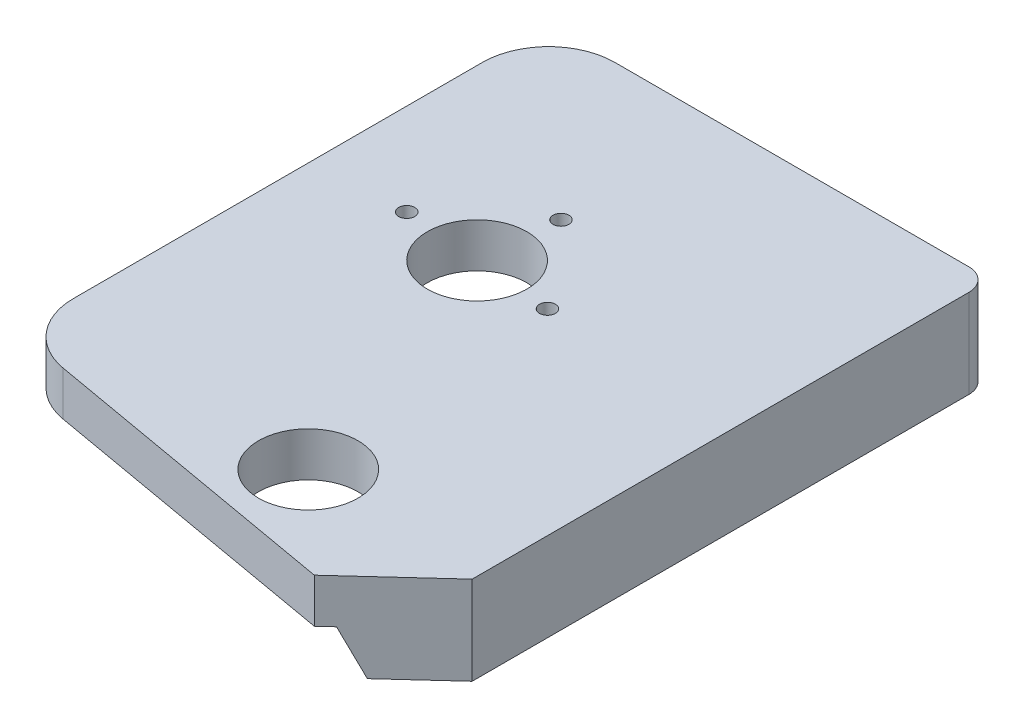
SolidWorks part; units mm, degrees
ref_plane "Front Plane" through (0, 0, 0) normal (0, 0, 1) x (1, 0, 0)
ref_plane "Top Plane" through (0, 0, 0) normal (0, 1, 0) x (1, 0, 0)
ref_plane "Right Plane" through (0, 0, 0) normal (1, 0, 0) x (0, 0, -1)
sketch "Sketch1" plane through (0, 0, 0) normal (0, 1, 0) x (1, 0, 0)
  line L0 (67.846, -67.54) -> (44.1988, -89.2087)
  line L1 (-43.412, -73.7605) -> (44.1988, -89.2087)
  line L2 (-59.154, -54.9999) -> (-59.154, 62.3652)
  line L3 (-40.104, 81.4152) -> (61.496, 81.4152)
  line L4 (67.846, -67.54) -> (67.846, 75.0652)
  line L5 (-59.154, -70.9848) -> (67.846, 81.4152) construction
  line L6 (-59.154, 81.4152) -> (67.846, -93.3783) construction
  line L7 (44.1988, -89.2087) -> (67.846, -93.3783) construction
  line L8 (67.846, -93.3783) -> (67.846, -67.54) construction
  arc A0 (61.496, 81.4152) -> (67.846, 75.0652) centre (61.496, 75.0652) cw
  arc A2 (-43.412, -73.7605) -> (-59.154, -54.9999) centre (-40.104, -54.9999) cw
  arc A3 (-59.154, 62.3652) -> (-40.104, 81.4152) centre (-40.104, 62.3652) cw
  point P0 (0, 0)
  dimension "D3" = 6.35
  dimension "D4" = 80
  dimension "D5" = 19.05
  dimension "D6" = 19.05
  dimension "D1" = 127
  dimension "D2" = 152.4
  dimension "D7" = 127.5
extrude "Initial Plate" add sketch "Sketch1" along normal blind 12.7
sketch "Sketch2" plane through (0, 12.7, 0) normal (0, 1, 0) x (1, 0, 0)
  line L0 (-43.412, -73.7605) -> (44.1988, -89.2087) construction
  line L1 (67.846, -67.54) -> (67.846, 75.0652) construction
  circle A1 centre (17.046, -63.7874) radius 14.2875
  circle A3 centre (17.046, -63.7874) radius 28.575 construction
  dimension "D1" = 28.575
  dimension "D2" = 57.15
  dimension "D3" = 20.32
  dimension "D4" = 50.8
extrude "Intake Bearing Hole" cut sketch "Sketch2" against normal through all
sketch "Sketch3" plane through (0, 0, 0) normal (0, 1, 0) x (1, 0, 0)
  line L0 (55.146, 81.4152) -> (55.146, -91.139)
  line L1 (61.496, 81.4152) -> (-40.104, 81.4152) construction
  line L2 (-43.412, -73.7605) -> (44.1988, -89.2087) construction
  line L3 (67.846, -67.54) -> (67.846, 75.0652) construction
  line L8 (61.496, 81.4152) -> (-40.104, 81.4152)
  line L9 (-59.154, 62.3652) -> (-59.154, -54.9999)
  line L10 (-43.412, -73.7605) -> (44.1988, -89.2087)
  line L11 (67.846, -67.54) -> (67.846, 75.0652)
  line L12 (55.146, 81.4152) -> (-40.104, 81.4152)
  line L13 (-59.154, 62.3652) -> (-59.154, -54.9999)
  line L14 (-43.412, -73.7605) -> (55.146, -91.139)
  line L16 (44.1988, -89.2087) -> (67.846, -67.54)
  arc A4 (67.846, 75.0652) -> (61.496, 81.4152) centre (61.496, 75.0652) ccw
  arc A5 (-40.104, 81.4152) -> (-59.154, 62.3652) centre (-40.104, 62.3652) ccw
  arc A6 (-59.154, -54.9999) -> (-43.412, -73.7605) centre (-40.104, -54.9999) ccw
  arc A9 (-40.104, 81.4152) -> (-59.154, 62.3652) centre (-40.104, 62.3652) ccw
  arc A10 (-59.154, -54.9999) -> (-43.412, -73.7605) centre (-40.104, -54.9999) ccw
  arc M33 (61.496, 81.4152) -> (67.846, 75.0652) centre (61.496, 75.0652) cw
  line M34 (67.846, 75.0652) -> (67.846, -67.54)
  line M35 (67.846, -67.54) -> (44.1988, -89.2087)
  line M36 (44.1988, -89.2087) -> (-43.412, -73.7605)
  line M40 (-40.104, 81.4152) -> (61.496, 81.4152)
  dimension "D1" = 12.7
  dimension "D2" = 0
extrude "Corner Mounting" [suppressed] add sketch "Sketch3" against normal blind 12.7
extrude "Boss-Extrude1" add sketch "Sketch3<3>" against normal blind 12.7 from surface contours L0 M40 M33 M34 M35 M36 region at (61.3943, 0, -3.6557) starting at face at (17.046, 0, 78.0749)
sketch "Sketch3<3>" plane through (0, 0, 0) normal (0, 1, 0) x (1, 0, 0) same geometry as "Sketch3"
chamfer "Corner Chamfer" [suppressed] distance 7.62 angle 70
chamfer "Right Corner Chamfer" distance 7.62 angle 70 1 edges at (55.146, 0, -1.1189) first distance on face at (17.046, 0, 78.0749)
sketch "Sketch4" plane through (0, 0, 0) normal (0, -1, 0) x (1, 0, 0)
  line L0 (17.046, 63.7874) -> (-10.6885, -12.4126) construction
  line L5 (11.4519, -10.4755) -> (-32.8289, -14.3496) construction
  line L6 (-12.6256, 9.7279) -> (-8.7515, -34.553) construction
  line L8 (47.526, -81.4152) -> (47.526, 86.1598) construction
  circle A0 centre (-10.6885, -12.4126) radius 14.2875
  circle A1 centre (17.046, 63.7874) radius 14.2875 construction
  circle A4 centre (11.4519, -10.4755) radius 2.286
  circle A5 centre (-8.7515, -34.553) radius 2.286
  circle A6 centre (-32.8289, -14.3496) radius 2.286
  point P18 (-10.6885, -12.4126)
  point P21 (-10.6885, -12.4126)
  dimension "D2" = 20
  dimension "D6" = 4.572
  dimension "D1" = 76.2
  dimension "D5" = 65
  dimension "D7" = 44.45
extrude "Cut-Extrude1" cut sketch "Sketch4" against normal through all
